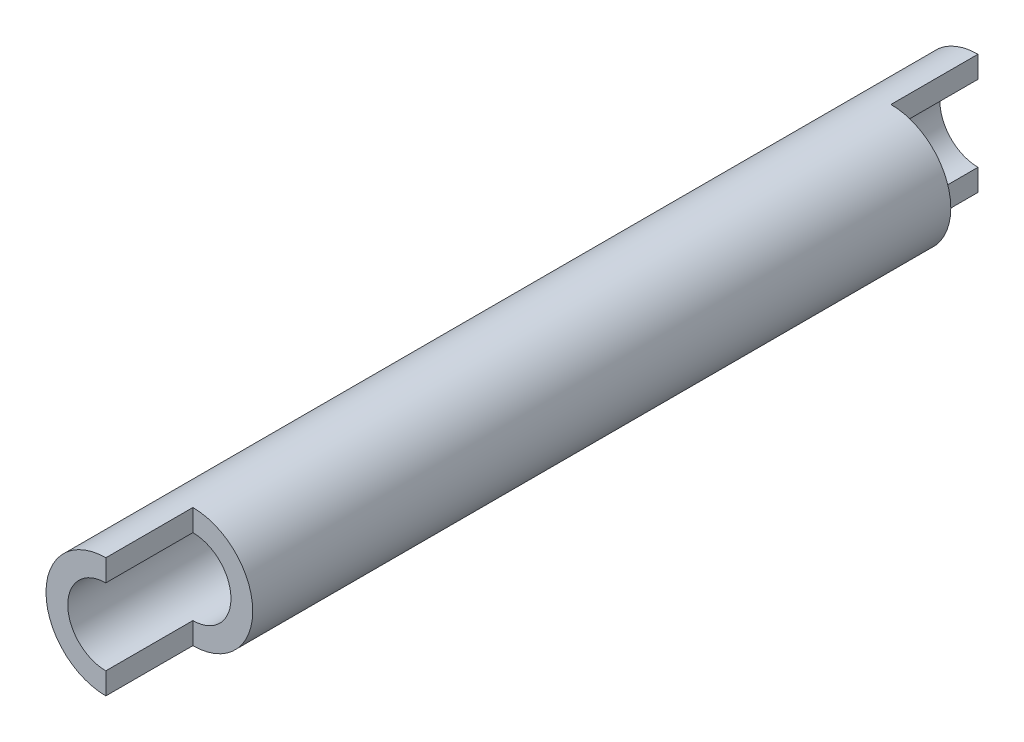
SolidWorks part; units mm, degrees
ref_plane "Płaszczyzna przednia" through (0, 0, 0) normal (0, 0, 1) x (1, 0, 0)
ref_plane "Płaszczyzna górna" through (0, 0, 0) normal (0, 1, 0) x (1, 0, 0)
ref_plane "Płaszczyzna prawa" through (0, 0, 0) normal (1, 0, 0) x (0, 0, -1)
sketch "Sketch1" plane through (0, 0, 0) normal (0, 0, 1) x (1, 0, 0)
  line L0 (-5.5, 0) -> (0, 0) construction
  line L1 (0, 0) -> (0, -5.5) construction
  circle A1 centre (0, 0) radius 3.5
  circle A2 centre (0, 0) radius 5.5
  dimension "D1" = 7
  dimension "D2" = 11
extrude "Boss-Extrude1 dlugosc calkowita" add sketch "Sketch1" along normal blind 64.16
sketch "Sketch2" plane through (0, 0, 0) normal (0, 0, -1) x (-1, 0, 0)
  line L0 (0, 5.5) -> (0, 3.5)
  line L1 (0, -3.5) -> (0, -5.5)
  arc A0 (0, -5.5) -> (0, 5.5) centre (0, 0) ccw
  arc A1 (0, -3.5) -> (0, 3.5) centre (0, 0) ccw
  circle A2 centre (0, 0) radius 5.5 construction
  dimension "D1" = 5.5
  dimension "D2" = 3.5
extrude "Boss-Extrude2 przedluzenie do montazu" add sketch "Sketch2" along normal blind 8 and the other way offset from surface (72.16 mm away) 8 other way up to face at (5.5, 0, 64.16)
sketch "koniec1" plane through (0, 0, 64.16) normal (0, 0, 1) x (1, 0, 0)
  line L0 (3.5, 0) -> (0, 0) construction
  line L1 (0, 0) -> (0, -3.5) construction
  arc A0 (0, -3.5) -> (0, 3.5) centre (0, 0) ccw construction
sketch "koniec2" plane through (0, 0, 0) normal (0, 0, -1) x (-1, 0, 0)
  line L0 (-3.5, 0) -> (0, 0) construction
  line L1 (0, 0) -> (0, 3.5) construction
  arc A0 (0, 3.5) -> (0, -3.5) centre (0, 0) ccw construction
equation "\"D1@Boss-Extrude1 dlugosc calkowita\" = \"dlugosc S3\""
equation "\"dlugosc S3\"=64.16"
equation "\"dlugosc S4\"= 150"
equation "\"dlugosc S1\"= 1"
equation "\"dlugosc S2\"= 50"
